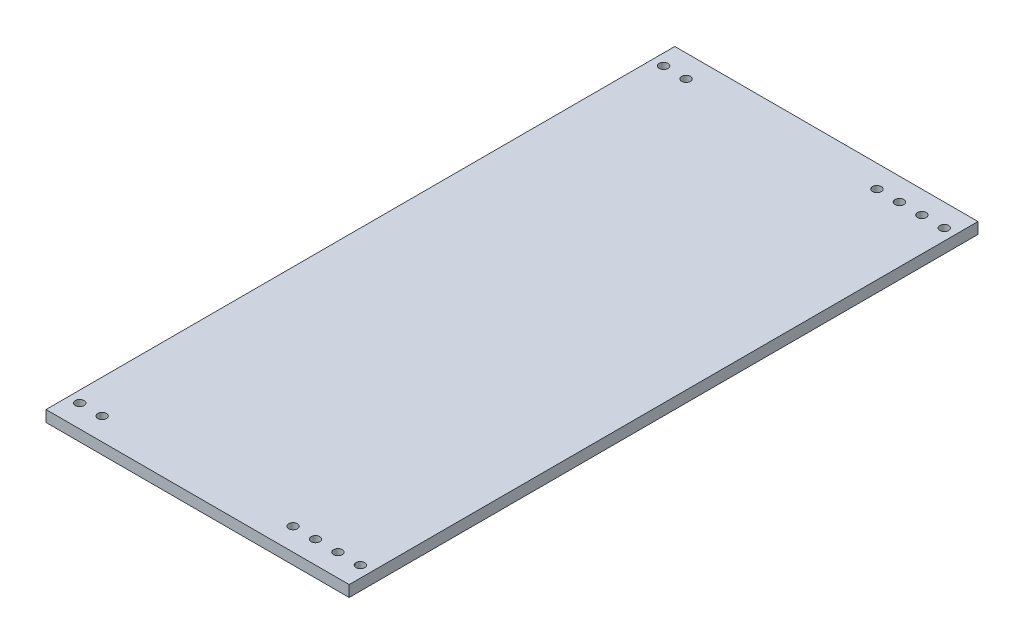
SolidWorks part; units mm, degrees
material "PC High Viscosity"
ref_plane "Front Plane" through (0, 0, 0) normal (0, 0, 1) x (1, 0, 0)
ref_plane "Top Plane" through (0, 0, 0) normal (0, 1, 0) x (1, 0, 0)
ref_plane "Right Plane" through (0, 0, 0) normal (1, 0, 0) x (0, 0, -1)
sketch "Sketch1" plane through (0, 0, 0) normal (0, 1, 0) x (1, 0, 0)
  line L1 (-85.725, -177.8) -> (85.725, -177.8)
  line L2 (-85.725, -177.8) -> (-85.725, 177.8)
  line L3 (-85.725, 177.8) -> (85.725, 177.8)
  line L4 (85.725, -177.8) -> (85.725, 177.8)
  line L5 (-85.725, -177.8) -> (85.725, 177.8) construction
  line L6 (-85.725, 177.8) -> (85.725, -177.8) construction
  point P0 (0, 0)
  dimension "D1" = 171.45
  dimension "D2" = 355.6
extrude "Boss-Extrude1" add sketch "Sketch1" along normal blind 6.35
sketch "Sketch2" plane through (0, 6.35, 0) normal (0, 1, 0) x (1, 0, 0)
  line L0 (85.725, -177.8) -> (85.725, 177.8) construction
  line L1 (-85.725, -177.8) -> (85.725, -177.8) construction
  line L2 (-85.725, 0) -> (85.725, 0) construction
  line L3 (-85.725, 177.8) -> (-85.725, -177.8) construction
  line L4 (0, 177.8) -> (0, -177.8) construction
  line L5 (85.725, 177.8) -> (-85.725, 177.8) construction
  circle A0 centre (79.375, -165.1) radius 2.4892
  circle A1 centre (66.675, -165.1) radius 2.4892
  circle A2 centre (53.975, -165.1) radius 2.4892
  circle A3 centre (41.275, -165.1) radius 2.4892
  circle A4 centre (79.375, 165.1) radius 2.4892
  circle A5 centre (66.675, 165.1) radius 2.4892
  circle A6 centre (53.975, 165.1) radius 2.4892
  circle A7 centre (41.275, 165.1) radius 2.4892
  circle A8 centre (79.375, 165.1) radius 2.4892
  circle A9 centre (66.675, 165.1) radius 2.4892
  circle A10 centre (53.975, 165.1) radius 2.4892
  circle A11 centre (41.275, 165.1) radius 2.4892
  circle A12 centre (-79.375, -165.1) radius 2.4892
  circle A13 centre (-66.675, -165.1) radius 2.4892
  circle A14 centre (-53.975, -165.1) radius 2.4892 construction
  circle A15 centre (-41.275, -165.1) radius 2.4892 construction
  circle A16 centre (-79.375, 165.1) radius 2.4892
  circle A17 centre (-66.675, 165.1) radius 2.4892
  circle A18 centre (-53.975, 165.1) radius 2.4892 construction
  circle A19 centre (-41.275, 165.1) radius 2.4892 construction
  dimension "D1" = 4.9784
  dimension "D2" = 6.35
  dimension "D3" = 12.7
  dimension "D5" = 12.7
  dimension "D4" = 4
extrude "Cut-Extrude2" cut sketch "Sketch2" against normal through all contours A15 | A14 | A13 | A12 | A4 | A5 | A6 | A7 | A16 | A17 | A18 | A19 | A3 | A2 | A1 | A0 region at (79.375, 6.35, -165.1) region at (66.675, 6.35, -165.1) region at (53.975, 6.35, -165.1) region at (41.275, 6.35, -165.1) region at (-79.375, 6.35, 165.1) region at (-66.675, 6.35, 165.1) region at (-79.375, 6.35, -165.1) region at (-66.675, 6.35, -165.1)
